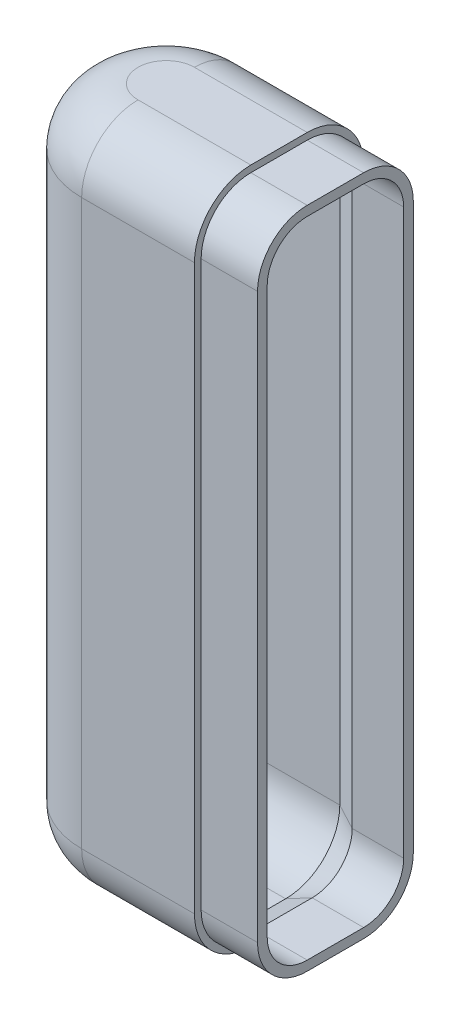
SolidWorks part; units mm, degrees
ref_plane "Front Plane" through (0, 0, 0) normal (0, 0, 1) x (1, 0, 0)
ref_plane "Top Plane" through (0, 0, 0) normal (0, 1, 0) x (1, 0, 0)
ref_plane "Right Plane" through (0, 0, 0) normal (1, 0, 0) x (0, 0, -1)
sketch "Sketch1" plane through (0, 0, 0) normal (0, 1, 0) x (1, 0, 0)
  line L0 (0, 19.05) -> (0, -19.05) construction
  line L1 (0, -19.05) -> (25.4, -19.05)
  line L2 (25.4, -19.05) -> (25.4, 19.05)
  line L3 (25.4, 19.05) -> (0, 19.05)
  arc A0 (0, 19.05) -> (0, -19.05) centre (0, 0) ccw
  dimension "D1" = 38.1
  dimension "D2" = 25.4
extrude "Boss-Extrude1" add sketch "Sketch1" along normal mid plane 152.4
fillet "Fillet1" radius 12.7 6 edges at (12.7, 76.2, -19.05) (12.7, 76.2, 19.05) (12.7, -76.2, -19.05) (12.7, -76.2, 19.05) (-19.05, 76.2, 0) (-19.05, -76.2, 0)
shell "Shell1" thickness 0.508 removed face at (25.4, 0, 0)
sketch "Sketch4" plane through (25.4, 0, 0) normal (1, 0, 0) x (0, 0, -1)
  line L0 (6.35, -75.692) -> (-6.35, -75.692) construction
  line L1 (-18.542, 63.5) -> (-18.542, -63.5) construction
  line L2 (18.542, -63.5) -> (18.542, 63.5) construction
  line L3 (-6.35, 75.692) -> (6.35, 75.692) construction
  line L4 (6.35, -75.692) -> (-6.35, -75.692)
  line L5 (-18.542, 63.5) -> (-18.542, -63.5)
  line L6 (18.542, -63.5) -> (18.542, 63.5)
  line L7 (-6.35, 75.692) -> (6.35, 75.692)
  arc A1 (-18.542, -63.5) -> (-6.35, -75.692) centre (-6.35, -63.5) ccw construction
  arc A2 (6.35, -75.692) -> (18.542, -63.5) centre (6.35, -63.5) ccw construction
  arc A3 (-6.35, 75.692) -> (-18.542, 63.5) centre (-6.35, 63.5) ccw construction
  arc A4 (18.542, 63.5) -> (6.35, 75.692) centre (6.35, 63.5) ccw construction
  arc A5 (-18.542, -63.5) -> (-6.35, -75.692) centre (-6.35, -63.5) ccw
  arc A6 (6.35, -75.692) -> (18.542, -63.5) centre (6.35, -63.5) ccw
  arc A7 (-6.35, 75.692) -> (-18.542, 63.5) centre (-6.35, 63.5) ccw
  arc A8 (18.542, 63.5) -> (6.35, 75.692) centre (6.35, 63.5) ccw
extrude "Extrude-Thin1" add sketch "Sketch4" along normal blind 12.7 and the other way blind 6.35 thin thin type one direction reverse wall 3.175
chamfer "Chamfer1" distance 7.46 angle 28 8 edges at (19.05, 0, -15.367) (19.05, 69.876, -12.726) (19.05, -69.876, -12.726) (19.05, 72.517, 0) (19.05, -72.517, 0) (19.05, 69.876, 12.726) (19.05, -69.876, 12.726) (19.05, 0, 15.367) first distance on face at (28.575, 0, -15.367) first distance on face at (28.575, 68.9422, -11.7922) first distance on face at (28.575, -68.9422, -11.7922) first distance on face at (28.575, 72.517, 0) first distance on face at (28.575, -72.517, 0) first distance on face at (28.575, 68.9422, 11.7922) first distance on face at (28.575, -68.9422, 11.7922) first distance on face at (28.575, 0, 15.367)
sketch "Sketch10" plane through (38.1, 0, 0) normal (1, 0, 0) x (0, 0, -1)
  line L0 (-6.35, -75.692) -> (6.35, -75.692) construction
  line L1 (18.542, 63.5) -> (18.542, -63.5) construction
  line L2 (-18.542, 63.5) -> (-18.542, -63.5) construction
  line L3 (6.35, 75.692) -> (-6.35, 75.692) construction
  line L4 (-6.35, -75.692) -> (6.35, -75.692)
  line L5 (18.542, 63.5) -> (18.542, -63.5)
  line L6 (-18.542, 63.5) -> (-18.542, -63.5)
  line L7 (6.35, 75.692) -> (-6.35, 75.692)
  arc A0 (-18.542, -63.5) -> (-6.35, -75.692) centre (-6.35, -63.5) ccw construction
  arc A1 (6.35, -75.692) -> (18.542, -63.5) centre (6.35, -63.5) ccw construction
  arc A2 (18.542, 63.5) -> (6.35, 75.692) centre (6.35, 63.5) ccw construction
  arc A3 (-6.35, 75.692) -> (-18.542, 63.5) centre (-6.35, 63.5) ccw construction
  arc A4 (-18.542, -63.5) -> (-6.35, -75.692) centre (-6.35, -63.5) ccw
  arc A5 (6.35, -75.692) -> (18.542, -63.5) centre (6.35, -63.5) ccw
  arc A6 (18.542, 63.5) -> (6.35, 75.692) centre (6.35, 63.5) ccw
  arc A7 (-6.35, 75.692) -> (-18.542, 63.5) centre (-6.35, 63.5) ccw
extrude "Cut-Extrude-Thin1" cut sketch "Sketch10" against normal up to surface (12.7 mm away) thin up to face at (25.4, 0, 0) thin type one direction reverse wall 1
